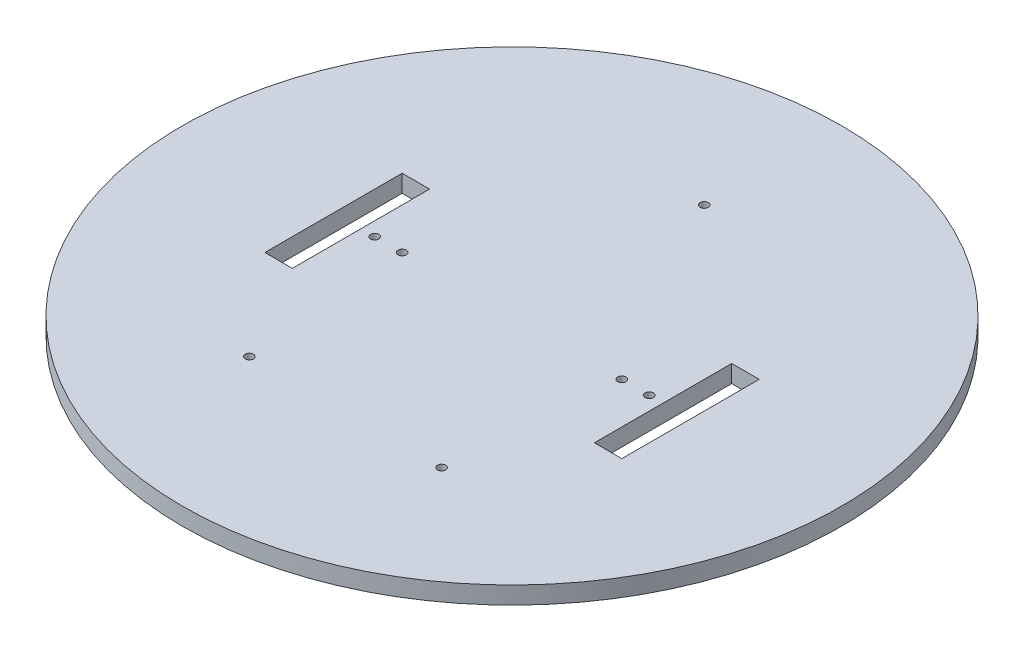
SolidWorks part; units mm, degrees
material "Delrin 2700 NC010, Low Viscosity Acetal Copolymer (SS)"
ref_plane "Front Plane" through (0, 0, 0) normal (0, 0, 1) x (1, 0, 0)
ref_plane "Top Plane" through (0, 0, 0) normal (0, 1, 0) x (1, 0, 0)
ref_plane "Right Plane" through (0, 0, 0) normal (1, 0, 0) x (0, 0, -1)
sketch "Sketch1" plane through (0, 0, 0) normal (0, 1, 0) x (1, 0, 0)
  circle A0 centre (0, 0) radius 120
  dimension "D1" = 240
extrude "Boss-Extrude1" add sketch "Sketch1" along normal blind 6.35
sketch "Sketch2" plane through (0, 6.35, 0) normal (0, 1, 0) x (1, 0, 0)
  line L0 (120, 0) -> (-120, 0) construction
  line L1 (0, 120) -> (0, -120) construction
  line L2 (65, -25) -> (55, 25) construction
  line L3 (-65, 25) -> (-55, 25)
  line L4 (-65, 25) -> (-65, -25)
  line L5 (-65, -25) -> (-55, -25)
  line L6 (-55, 25) -> (-55, -25)
  line L7 (-65, 25) -> (-55, -25) construction
  line L8 (-65, -25) -> (-55, 25) construction
  line L9 (65, 25) -> (55, -25) construction
  line L10 (55, 25) -> (55, -25)
  line L11 (65, -25) -> (55, -25)
  line L12 (65, 25) -> (65, -25)
  line L13 (65, 25) -> (55, 25)
  circle A0 centre (0, 0) radius 120 construction
  point P7 (-60, 0)
  point P17 (60, 0)
  dimension "D1" = 10
  dimension "D2" = 50
  dimension "D3" = 60
extrude "Cut-Extrude1" cut sketch "Sketch2" against normal through all
sketch "Sketch3" plane through (0, 6.35, 0) normal (0, 1, 0) x (1, 0, 0)
  line L0 (0, 0) -> (0, 120) construction
  line L1 (0, 0) -> (-60, -103.923) construction
  line L2 (0, 0) -> (60, -103.923) construction
  circle A0 centre (0, 0) radius 120 construction
  circle A1 centre (0, 70) radius 1.5
  circle A2 centre (-35, -60.6218) radius 1.5
  circle A3 centre (35, -60.6218) radius 1.5
  dimension "D1" = 3
  dimension "D5" = 3
  dimension "D6" = 3
  dimension "D2" = 50
  dimension "D3" = 150
  dimension "D4" = 150
  dimension "D7" = 50
  dimension "D8" = 50
extrude "Cut-Extrude2" cut sketch "Sketch3" against normal through all
sketch "Sketch4" plane through (0, 0, 0) normal (0, -1, 0) x (1, 0, 0)
  line L0 (-120, 0) -> (120, 0) construction
  line L1 (0, 120) -> (0, -120) construction
  circle A0 centre (0, 0) radius 120 construction
  circle A1 centre (-50, 0) radius 1.5
  circle A2 centre (-40, 0) radius 1.5
  circle A3 centre (40, 0) radius 1.5
  circle A4 centre (50, 0) radius 1.5
  point P11 (0, 0)
  dimension "D1" = 3
  dimension "D2" = 3
  dimension "D3" = 10
  dimension "D4" = 40
extrude "Cut-Extrude3" cut sketch "Sketch4" against normal through all
